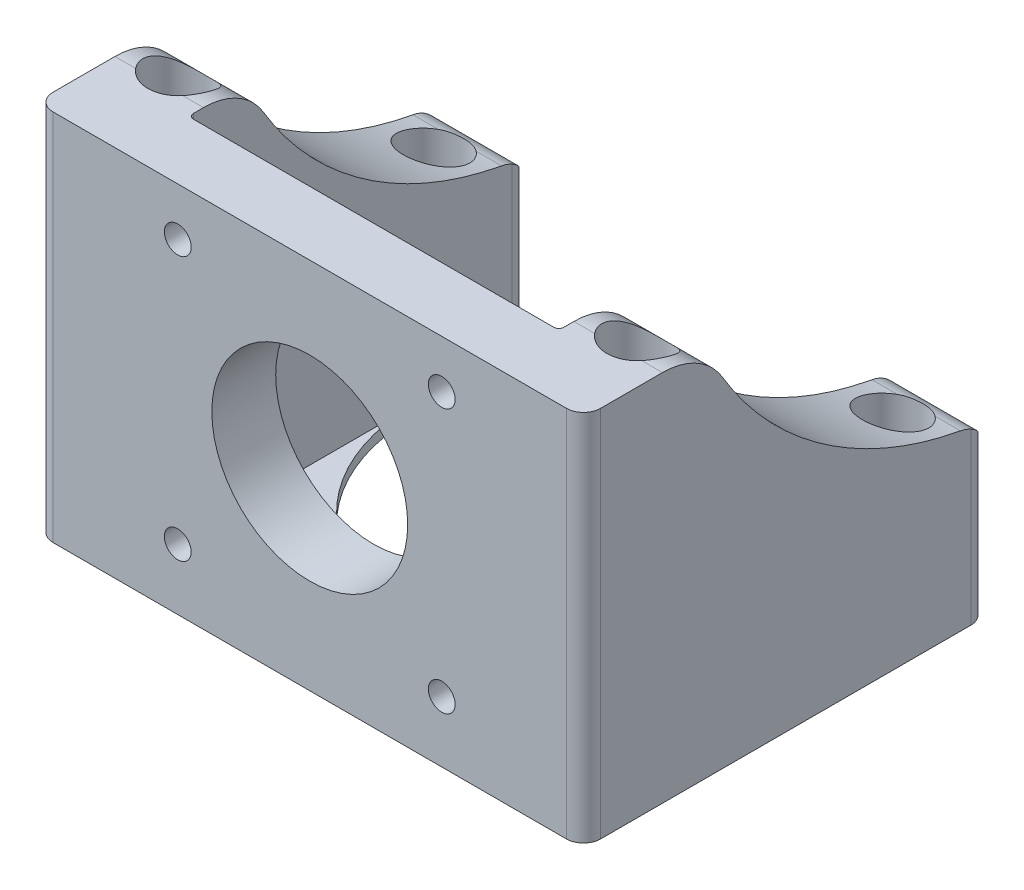
SolidWorks part; units mm, degrees
note: The reader was unsure of these and kept them because the rebuilt part matched: shared geometry of "Sketch5<3>".
ref_plane "Front Plane" through (0, 0, 0) normal (0, 0, 1) x (1, 0, 0)
ref_plane "Top Plane" through (0, 0, 0) normal (0, 1, 0) x (1, 0, 0)
ref_plane "Right Plane" through (0, 0, 0) normal (1, 0, 0) x (0, 0, -1)
sketch "Main Face" plane through (0, 0, 0) normal (0, 0, 1) x (1, 0, 0)
  line L0 (0, 0) -> (0, 36.6282) construction
  line L1 (0, 0) -> (42.2877, 0) construction
  line L2 (0, 0) -> (32.6841, 32.6841) construction
  line L3 (0, 21.15) -> (21.15, 21.15)
  line L4 (21.15, 0) -> (21.15, 21.15)
  line L5 (0, 15.5) -> (15.5, 15.5) construction
  line L6 (15.5, 15.5) -> (15.5, 0) construction
  line L7 (21.15, 0) -> (21.15, -21.15)
  line L8 (0, -21.15) -> (21.15, -21.15)
  line L9 (15.5, 0) -> (15.5, -15.5) construction
  line L10 (15.5, -15.5) -> (0, -15.5) construction
  line L11 (0, -21.15) -> (-21.15, -21.15)
  line L12 (-21.15, 0) -> (-21.15, -21.15)
  line L13 (0, -15.5) -> (-15.5, -15.5) construction
  line L14 (-15.5, -15.5) -> (-15.5, 0) construction
  line L15 (-21.15, 0) -> (-21.15, 21.15)
  line L16 (0, 21.15) -> (-21.15, 21.15)
  line L17 (-15.5, 0) -> (-15.5, 15.5) construction
  line L18 (-15.5, 15.5) -> (0, 15.5) construction
  circle A0 centre (15.5, 15.5) radius 1.575
  circle A1 centre (15.5, -15.5) radius 1.575
  circle A2 centre (-15.5, -15.5) radius 1.575
  circle A3 centre (-15.5, 15.5) radius 1.575
  circle A4 centre (0, 0) radius 11.5
  point P36 (0, 0)
  dimension "D3" = 3.15
  dimension "D5" = 23
  dimension "D1" = 15.5
  dimension "D2" = 21.15
  dimension "D4" = 4
extrude "MainFace" add sketch "Main Face" along normal blind 7.5
sketch "Sketch2" plane through (-21.15, 0, 0) normal (-1, 0, 0) x (0, 0, 1)
  line L0 (7.5, 21.15) -> (-1.7717, 21.15)
  line L1 (7.5, -21.15) -> (-40, -21.15)
  line L2 (0, 21.15) -> (0, -21.15) construction
  line L3 (-40, -21.15) -> (-40, -6.15)
  line L8 (0, 21.15) -> (0, -21.15)
  line L9 (0, -21.15) -> (7.5, -21.15)
  line L10 (7.5, -21.15) -> (7.5, 21.15)
  line L11 (7.5, 21.15) -> (0, 21.15)
  line L12 (0, 21.15) -> (0, -21.15)
  line L13 (0, -21.15) -> (7.5, -21.15)
  line L15 (7.5, 21.15) -> (0, 21.15)
  arc A0 (-40, -6.15) -> (-36.7684, -2.2727) centre (-36.0582, -6.15) cw
  arc A1 (-1.7717, 21.15) -> (-8.8257, 17.1424) centre (-1.7717, 12.9382) ccw
  arc A2 (-8.8257, 17.1424) -> (-36.7684, -2.2727) centre (-44.185, 38.217) cw
  line M3 (0, 21.15) -> (0, -21.15)
  line M4 (0, -21.15) -> (7.5, -21.15)
  line M5 (7.5, -21.15) -> (7.5, 21.15)
  line M6 (7.5, 21.15) -> (0, 21.15)
  dimension "D1" = 40
  dimension "D2" = 15
  dimension "D3" = 0
extrude "SideProfile" add sketch "Sketch2" along normal blind 11 contours M6 M3 M4 M5 | A1 A2 A0 L3 L1 L0 M3
sketch "Sketch3" plane through (0, 21.15, 0) normal (0, 1, 0) x (1, 0, 0)
  line L0 (-21.75, 0.6) -> (-21.75, 41.9381)
  line L1 (21.15, 0) -> (-21.15, 0) construction
  line L2 (-21.15, 1.7717) -> (-21.15, 8.8257) construction
  line L3 (-21.75, 41.9381) -> (-16.9322, 41.9381)
  line L4 (-16.9322, 41.9381) -> (-16.9322, 2.9783)
  line L5 (-16.9322, 2.9783) -> (-21.15, 0)
  arc A0 (-21.15, 0) -> (-21.75, 0.6) centre (-21.15, 0.6) cw
  dimension "D1" = 0.6
extrude "Non-interfering fillet" cut sketch "Sketch3" against normal through all both and the other way through all
mirror "Mirror1" about plane through (0, 0, 0) normal (1, 0, 0) of "SideProfile", "Non-interfering fillet"
sketch "Sketch4" plane through (0, -21.15, 0) normal (0, -1, 0) x (1, 0, 0)
  line L8 (21.75, -0.6) -> (21.75, -40)
  line L9 (21.75, -40) -> (32.15, -40)
  line L10 (32.15, -40) -> (32.15, 7.5)
  line L11 (32.15, 7.5) -> (-32.15, 7.5)
  line L12 (-32.15, 7.5) -> (-32.15, -40)
  line L13 (-32.15, -40) -> (-21.75, -40)
  line L14 (-21.75, -40) -> (-21.75, -0.6)
  line L15 (-21.15, 0) -> (21.15, 0)
  line L16 (21.75, -0.6) -> (21.75, -40)
  line L17 (21.75, -40) -> (32.15, -40)
  line L18 (32.15, -40) -> (32.15, 7.5)
  line L19 (32.15, 7.5) -> (-32.15, 7.5)
  line L20 (-32.15, 7.5) -> (-32.15, -40)
  line L21 (-32.15, -40) -> (-21.75, -40)
  line L22 (-21.75, -40) -> (-21.75, -0.6)
  line L23 (-21.15, 0) -> (21.15, 0)
  arc A2 (21.75, -0.6) -> (21.15, 0) centre (21.15, -0.6) ccw
  arc A3 (-21.15, 0) -> (-21.75, -0.6) centre (-21.15, -0.6) ccw
  arc A4 (21.75, -0.6) -> (21.15, 0) centre (21.15, -0.6) ccw
  arc A5 (-21.15, 0) -> (-21.75, -0.6) centre (-21.15, -0.6) ccw
  dimension "D1" = 0
extrude "BaseClearance" add sketch "Sketch4" along normal blind 1.5
sketch "Sketch5" plane through (0, -22.65, 0) normal (0, -1, 0) x (1, 0, 0)
  line L0 (0, 0) -> (-32.15, 0) construction
  line L1 (-32.15, 7.5) -> (-32.15, -40) construction
  line L2 (-26.95, 0) -> (-26.95, -40) construction
  line L3 (-32.15, -40) -> (-21.75, -40) construction
  line L4 (0, 0) -> (0, -31.6298) construction
  circle A0 centre (-26.95, -4) radius 3.55
  circle A1 centre (-26.95, -34) radius 3.55
  circle A2 centre (-26.95, -4) radius 1.575
  circle A3 centre (-26.95, -34) radius 1.575
  circle A4 centre (26.95, -34) radius 1.575
  circle A5 centre (26.95, -4) radius 1.575
  circle A6 centre (26.95, -34) radius 3.55
  circle A7 centre (26.95, -4) radius 3.55
  dimension "D3" = 7.1
  dimension "D4" = 3.15
  dimension "D1" = 4
  dimension "D2" = 6
extrude "GroudingBoltHoles" cut sketch "Sketch5" against normal through all both and the other way through all contours A2 | A3 | A4 | A5
extrude "BoltAccessHoles" cut sketch "Sketch5<3>" against normal blind 47.5 from offset 10 contours A1 A3 | A0 | A7 | A6 offset against normal yes
sketch "Sketch5<3>" plane through (0, -22.65, 0) normal (0, -1, 0) x (1, 0, 0) same geometry as "Sketch5"
fillet "HappyPrinterCurves" radius 2 6 edges at (-21.75, -14.4, -40) (32.15, -14.4, -40) (21.75, -14.4, -40) (-32.15, -14.4, -40) (32.15, -0.75, 7.5) (-32.15, -0.75, 7.5)
sketch "Sketch6" plane through (0, -22.65, 0) normal (0, -1, 0) x (1, 0, 0)
  line L0 (-30.15, -40) -> (-23.75, -40) construction
  line L1 (24.2949, 1.7498) -> (-24.4921, 1.7498)
  line L2 (24.2949, 1.7498) -> (24.2949, -40)
  line L3 (24.2949, -40) -> (-24.4921, -40)
  line L4 (-24.4921, 1.7498) -> (-24.4921, -40)
extrude "BasePlate" add sketch "Sketch6" against normal blind 1.2
sketch "Sketch7" plane through (0, -21.45, 0) normal (0, 1, 0) x (1, 0, 0)
  line L0 (21.75, 36.7684) -> (21.75, 8.8257) construction
  line L1 (21.75, 38) -> (21.75, 36.7684) construction
  line L2 (-21.75, 8.8257) -> (-21.75, 36.7684) construction
  line L3 (-21.75, 36.7684) -> (-21.75, 38) construction
  line L4 (21.75, 36.7684) -> (21.75, 26.4016)
  line L5 (21.75, 38) -> (21.75, 36.7684)
  line L6 (-21.75, 26.4016) -> (-21.75, 36.7684)
  line L7 (-21.75, 36.7684) -> (-21.75, 38)
  line L8 (0, 0) -> (0, 34.2235) construction
  line L9 (0, 4.6516) -> (-13.9295, 4.6516) construction
  line L10 (-23.75, 40) -> (-23.75, 46.1873)
  line L11 (-23.75, 46.1873) -> (23.75, 46.1873)
  line L12 (23.75, 46.1873) -> (23.75, 40)
  arc A0 (23.75, 40) -> (21.75, 38) centre (23.75, 38) ccw construction
  arc A1 (-21.75, 38) -> (-23.75, 40) centre (-23.75, 38) ccw construction
  arc A2 (23.75, 40) -> (21.75, 38) centre (23.75, 38) ccw
  arc A3 (-21.75, 38) -> (-23.75, 40) centre (-23.75, 38) ccw
  arc A4 (-21.75, 26.4016) -> (21.75, 26.4016) centre (0, 26.4016) ccw
extrude "SupportTorsionButBreathe" cut sketch "Sketch7" against normal through all
